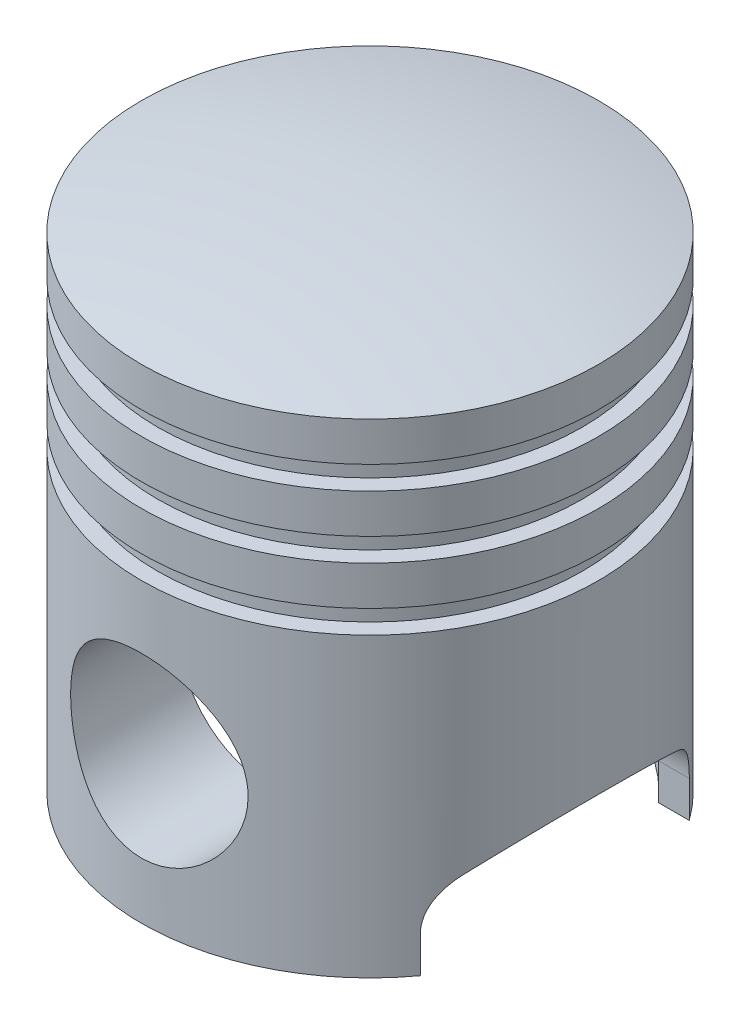
SolidWorks part; units mm, degrees
ref_plane "Front Plane" through (0, 0, 0) normal (0, 0, 1) x (1, 0, 0)
ref_plane "Top Plane" through (0, 0, 0) normal (0, 1, 0) x (1, 0, 0)
ref_plane "Right Plane" through (0, 0, 0) normal (1, 0, 0) x (0, 0, -1)
sketch "Sketch1" plane through (0, 0, 0) normal (0, 1, 0) x (1, 0, 0)
  circle A0 centre (0, 0) radius 42.5
  dimension "D1" = 85
extrude "Boss-Extrude1" add sketch "Sketch1" along normal blind 90
sketch "Sketch2" plane through (0, 90, 0) normal (0, 1, 0) x (1, 0, 0)
  circle A0 centre (0, 0) radius 39.5
  dimension "D1" = 79
extrude "Cut-Extrude1" cut sketch "Sketch2" against normal blind 4.3 from offset 7.3 flip side to cut offset against normal yes
pattern_linear "LPattern1" count 3 spacing 11.6 along (0, -1, 0) of "Cut-Extrude1"
sketch "Sketch3" plane through (0, 0, 0) normal (0, -1, 0) x (1, 0, 0)
  circle A0 centre (0, 0) radius 38
  dimension "D1" = 76
extrude "Cut-Extrude2" cut sketch "Sketch3" against normal blind 85
dome "Dome1" faces to dome 1 distance 5 reverse direction no elliptical dome no face at (0, 90, 42.5) parameters "D1"=5
sketch "Sketch4" plane through (0, 0, 0) normal (0, 0, 1) x (1, 0, 0)
  circle A0 centre (0, 27) radius 16.5
  dimension "D1" = 33
  dimension "D2" = 27
extrude "Cut-Extrude3" cut sketch "Sketch4" against normal through all both and the other way through all
sketch "Sketch5" plane through (0, 0, 0) normal (1, 0, 0) x (0, 0, -1)
  line L0 (0, 0) -> (0, 21.4369) construction
  line L1 (-25, 0) -> (-25, 12)
  line L2 (-42.5, 0) -> (42.5, 0) construction
  line L3 (25, 0) -> (25, 12)
  line L4 (-25, 0) -> (25, 0)
  arc A0 (-25, 12) -> (25, 12) centre (0, -19.225) cw
  dimension "D3" = 40
  dimension "D2" = 12
  dimension "D1" = 50
extrude "Cut-Extrude5" cut sketch "Sketch5" against normal through all both and the other way through all
fillet "Fillet1" radius 10 4 edges at (-31.4937, 12, -25) (-31.4937, 12, 25) (31.4937, 12, -25) (31.4937, 12, 25)
sketch "Sketch6" plane through (0, 0, 0) normal (0, 0, 1) x (1, 0, 0)
  circle A0 centre (0, 27) radius 16.5 construction
  circle A1 centre (0, 27) radius 16.5
  circle A2 centre (0, 27) radius 22.5
  dimension "D1" = 45
extrude "Boss-Extrude2" add sketch "Sketch6" along normal up to next from offset 19
mirror "Mirror1" about plane through (0, 0, 0) normal (0, 0, 1) of "Boss-Extrude2"
